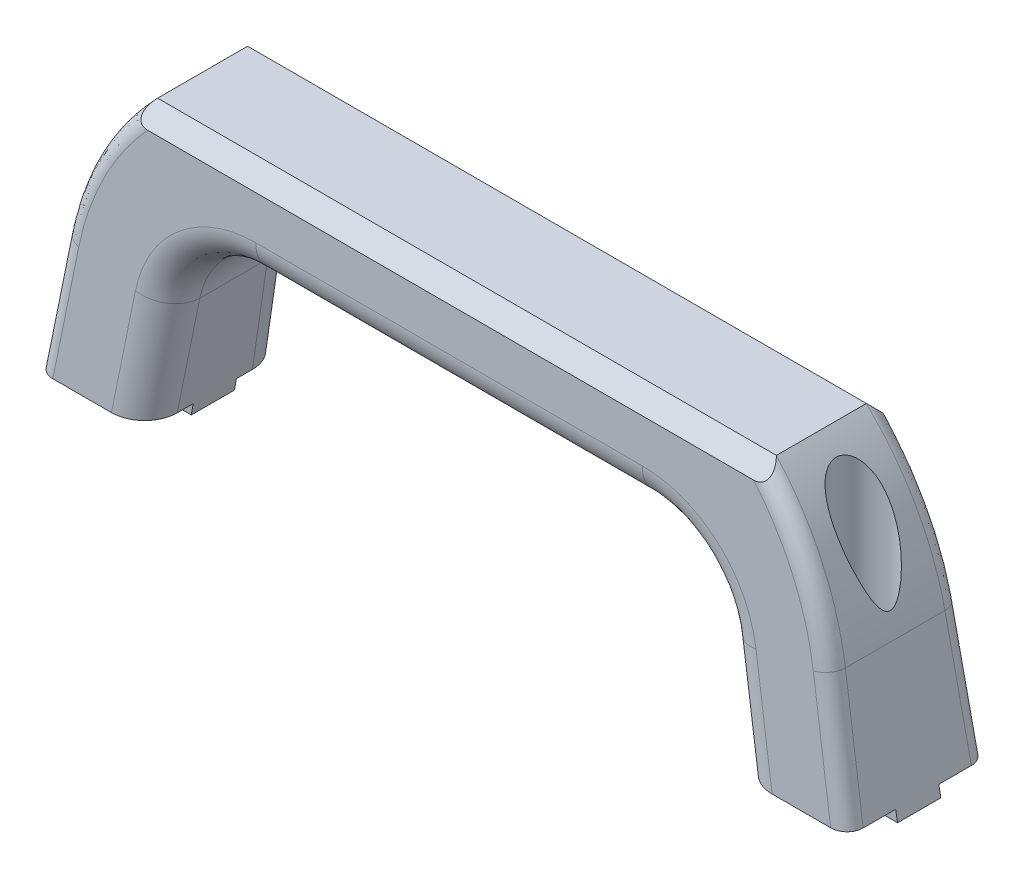
SolidWorks part; units mm, degrees
ref_plane "Front Plane" through (0, 0, 0) normal (0, 0, 1) x (1, 0, 0)
ref_plane "Top Plane" through (0, 0, 0) normal (0, 1, 0) x (1, 0, 0)
ref_plane "Right Plane" through (0, 0, 0) normal (1, 0, 0) x (0, 0, -1)
sketch "Sketch2" plane through (0, 0, 0) normal (0, 0, 1) x (1, 0, 0)
  line L0 (-55, 0) -> (-51.5125, 19.7784)
  line L1 (0, 33) -> (0, 0) construction
  line L3 (-35.7556, 33) -> (0, 33)
  line L5 (-55, 0) -> (-55, 33) construction
  line L6 (-75, 0) -> (-70.9095, 23.1986)
  line L7 (-57.2535, 50) -> (0, 50)
  line L8 (-55, 0) -> (-75, 0)
  line L10 (0, 50) -> (0, 33)
  line L11 (-57.2535, 50) -> (-55.3004, 52.0224) construction
  line L12 (-70.9095, 23.1986) -> (-51.5125, 19.7784) construction
  arc A0 (-51.5125, 19.7784) -> (-35.7556, 33) centre (-35.7556, 17) cw
  arc A1 (-70.9095, 23.1986) -> (-57.2535, 50) centre (-20.2497, 14.2659) cw
  point P2 (-65, 0)
  dimension "D3" = 46
  dimension "D5" = 16
  dimension "D6" = 33
  dimension "D1" = 130
  dimension "D2" = 10
  dimension "D4" = 17
  dimension "D7" = 20
extrude "Boss-Extrude1" add sketch "Sketch2" along normal mid plane 26 contours A1 L7 L10 L3 A0 L0 L8 L6
sketch "Sketch9" plane through (0, 0, 0) normal (1, 0, 0) x (0, 0, -1)
  line L0 (-13, 0) -> (-11.254, 50)
  line L1 (-13, 50) -> (13, 50) construction
  line L2 (-11.254, 50) -> (-13, 50)
  line L3 (-13, 50) -> (-13, 0)
  dimension "D1" = 2
extrude "Cut-Extrude6" cut sketch "Sketch9" against normal through all
mirror "Mirror4" about plane through (0, 0, 0) normal (0, 0, 1) of "Cut-Extrude6"
fillet "Fillet1" radius 6 6 edges at (-17.8778, 33, -11.8476) (-46.0402, 29.2567, -11.9783) (-17.8778, 33, 11.8476) (-46.0402, 29.2567, 11.9783) (-53.2563, 9.8892, -12.6547) (-53.2563, 9.8892, 12.6547)
fillet "Fillet3" radius 3 4 edges at (-72.9547, 11.5993, -12.5949) (-72.9547, 11.5993, 12.5949) (-66.0842, 37.6197, -11.6863) (-66.0842, 37.6197, 11.6863)
sketch "Sketch6" plane through (0, 0, 0) normal (0, -1, 0) x (1, 0, 0)
  line L0 (-75, 0) -> (-55, 0) construction
  line L1 (-75, 10.0164) -> (-75, -10.0164) construction
  line L2 (-55, 6.96) -> (-55, -6.96) construction
  circle A0 centre (-65, 0) radius 3
  dimension "D1" = 6
extrude "Cut-Extrude3" cut sketch "Sketch6" against normal through all
sketch "Sketch7" plane through (0, 0, 0) normal (0, -1, 0) x (1, 0, 0)
  circle A0 centre (-65, 0) radius 5
  dimension "D1" = 10
extrude "Cut-Extrude4" cut sketch "Sketch7" against normal through all from offset 15 offset against normal yes
sketch "Sketch8" plane through (0, 15, 0) normal (0, 1, 0) x (1, 0, 0)
  line L0 (-68, 4) -> (-68, -4)
  line L1 (-62, 4) -> (-62, -4)
  circle A0 centre (-65, 0) radius 5 construction
  circle A1 centre (-65, 0) radius 5 construction
  arc A2 (-68, -4) -> (-62, -4) centre (-65, 0) ccw
  arc A3 (-68, 4) -> (-62, 4) centre (-65, 0) cw
  circle A4 centre (-65, 0) radius 3 construction
extrude "Cut-Extrude5" cut sketch "Sketch8" against normal blind 1
sketch "Sketch10" plane through (0, 0, 0) normal (0, 0, 1) x (1, 0, 0)
  line L0 (-75, 0) -> (-75.3527, -2)
  line L1 (-75.3527, -2) -> (-70, -2)
  line L2 (-70, -2) -> (-68, 0)
  line L3 (-61.1295, 0) -> (-71.9722, 0) construction
  line L4 (-68, 0) -> (-75, 0)
  line L5 (-55, 0) -> (-55.3527, -2)
  line L6 (-55.3527, -2) -> (-60, -2)
  line L7 (-60, -2) -> (-62, 0)
  line L8 (-62, 0) -> (-55, 0)
  line L9 (-51.5125, 19.7784) -> (-55, 0) construction
  line L10 (-75, 0) -> (-70.9095, 23.1986) construction
  line L11 (-68, 0) -> (-62, 0) construction
  dimension "D1" = 45
  dimension "D2" = 45
  dimension "D3" = 2
extrude "Boss-Extrude2" add sketch "Sketch10" along normal mid plane 8
mirror "Mirror2" about plane through (0, 50, 13) normal (1, 0, 0) of bodies 113 101
sketch "Sketch3" plane through (0, 0, 0) normal (1, 0, 0) x (0, 0, -1)
  line L0 (-8.3249, 50) -> (-11.3599, 46.965)
  line L2 (-11.3249, 50) -> (-8.3249, 50)
  line L3 (-8.3249, 50) -> (8.3249, 50) construction
  line L4 (-9.2063, 23.1986) -> (-8.3249, 50) construction
  line L6 (-11.3249, 50) -> (-11.3599, 46.965)
  line L7 (-11.254, 50) -> (-12.2044, 22.7823) construction
  dimension "D1" = 3
  dimension "D2" = 45
extrude "Cut-Extrude1" cut sketch "Sketch3" against normal through all both and the other way through all
mirror "Mirror3" about plane through (0, 0, 0) normal (0, 0, 1) of "Cut-Extrude1"
